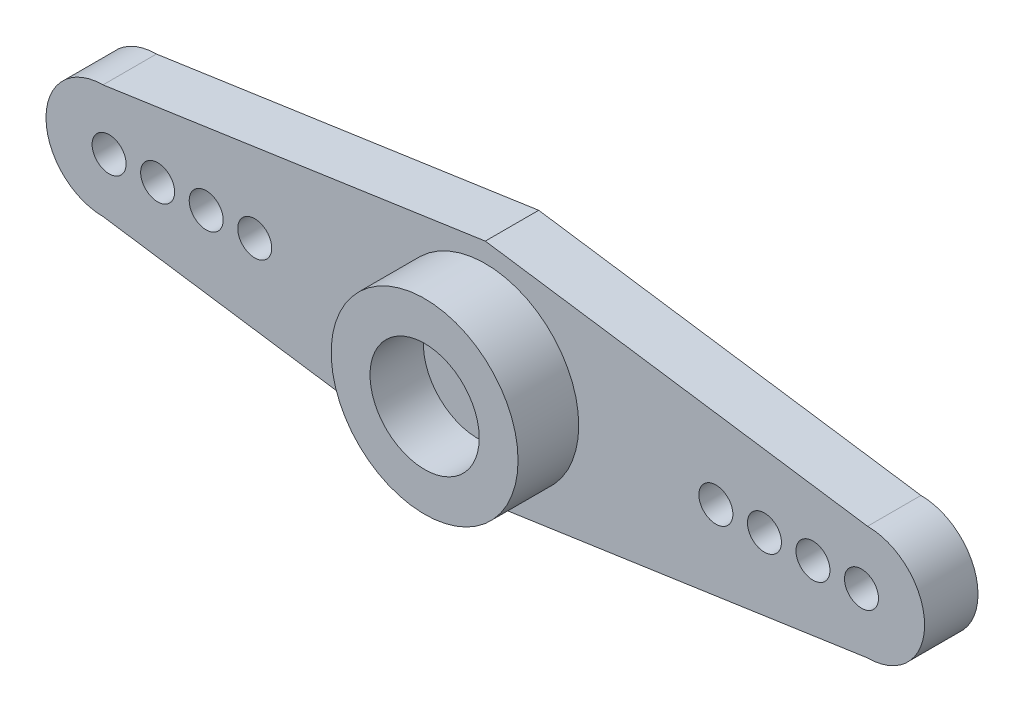
SolidWorks part; units mm, degrees
ref_plane "Front Plane" through (0, 0, 0) normal (0, 0, 1) x (1, 0, 0)
ref_plane "Top Plane" through (0, 0, 0) normal (0, 1, 0) x (1, 0, 0)
ref_plane "Right Plane" through (0, 0, 0) normal (1, 0, 0) x (0, 0, -1)
sketch "Sketch1" plane through (0, 0, 0) normal (0, 0, 1) x (1, 0, 0)
  line L1 (-22.987, -5.9055) -> (22.987, -5.9055)
  line L2 (-22.987, -5.9055) -> (-22.987, 5.9055)
  line L3 (-22.987, 5.9055) -> (22.987, 5.9055)
  line L4 (22.987, -5.9055) -> (22.987, 5.9055)
  line L5 (-22.987, -5.9055) -> (22.987, 5.9055) construction
  line L6 (-22.987, 5.9055) -> (22.987, -5.9055) construction
  point P0 (0, 0)
extrude "Extrude1" add sketch "Sketch1" along normal blind 5.969
sketch "Sketch2" plane through (0, 0, 5.969) normal (0, 0, 1) x (1, 0, 0)
  circle A0 centre (0, 0) radius 4.8895
extrude "Extrude2" cut sketch "Sketch2" against normal blind 3.175 flip side to cut
sketch "Sketch3" plane through (0, 0, 5.969) normal (0, 0, 1) x (1, 0, 0)
  circle A0 centre (0, 0) radius 2.8575
extrude "Extrude3" cut sketch "Sketch3" against normal blind 2.794
sketch "Sketch4" plane through (0, 0, 0) normal (0, 0, -1) x (-1, 0, 0)
  line L0 (0, 0) -> (-12.065, 0) construction
hole_wizard "#50 (0.07) Diameter Hole1" positions "3DSketch1" profile "Sketch5" hole size "#50" standard "Ansi Inch"
sketch3d "3DSketch1"
  point P0 (12.065, 0, 0)
sketch "Sketch5" plane through (12.065, 0, 0) normal (1, 0, 0) x (0, 1, 0)
  line L0 (0, 0) -> (0, 5.6142)
  line L1 (0, 5.6142) -> (0.889, 5.08)
  line L2 (0.889, 5.08) -> (0.889, 0)
  line L5 (0.889, 0) -> (0, 0)
  line L10 (0, 5.6142) -> (-0.889, 5.08) construction
  line L11 (0, -6.35) -> (0, 107.95) construction
  dimension "Hole Dia." = 1.778
  dimension "Hole Depth" = 5.08
  dimension "Drill Angle" = 118
pattern_linear "LPattern1" count 4 spacing 2.54 along (1, 0, 0) of "#50 (0.07) Diameter Hole1"
mirror "Mirror1" about plane through (0, 0, 0) normal (1, 0, 0) of "LPattern1"
sketch "Sketch6" plane through (0, 0, 0) normal (0, 0, -1) x (-1, 0, 0)
  line L0 (22.987, 0) -> (20.0025, 0) construction
  line L1 (22.987, 5.9055) -> (22.987, -5.9055) construction
  line L2 (20.0025, -2.9845) -> (0, -5.9055)
  line L3 (22.987, -5.9055) -> (-22.987, -5.9055) construction
  line L4 (20.0025, 2.9845) -> (0, 5.9055)
  line L5 (-22.987, 5.9055) -> (22.987, 5.9055) construction
  arc A0 (22.987, 0) -> (20.0025, -2.9845) centre (20.0025, 0) cw
  arc A1 (22.987, 0) -> (20.0025, 2.9845) centre (20.0025, 0) ccw
extrude "Extrude4" cut sketch "Sketch6" against normal through all flip side to cut
mirror "Mirror2" about plane through (0, 0, 0) normal (1, 0, 0) of "Extrude4"
